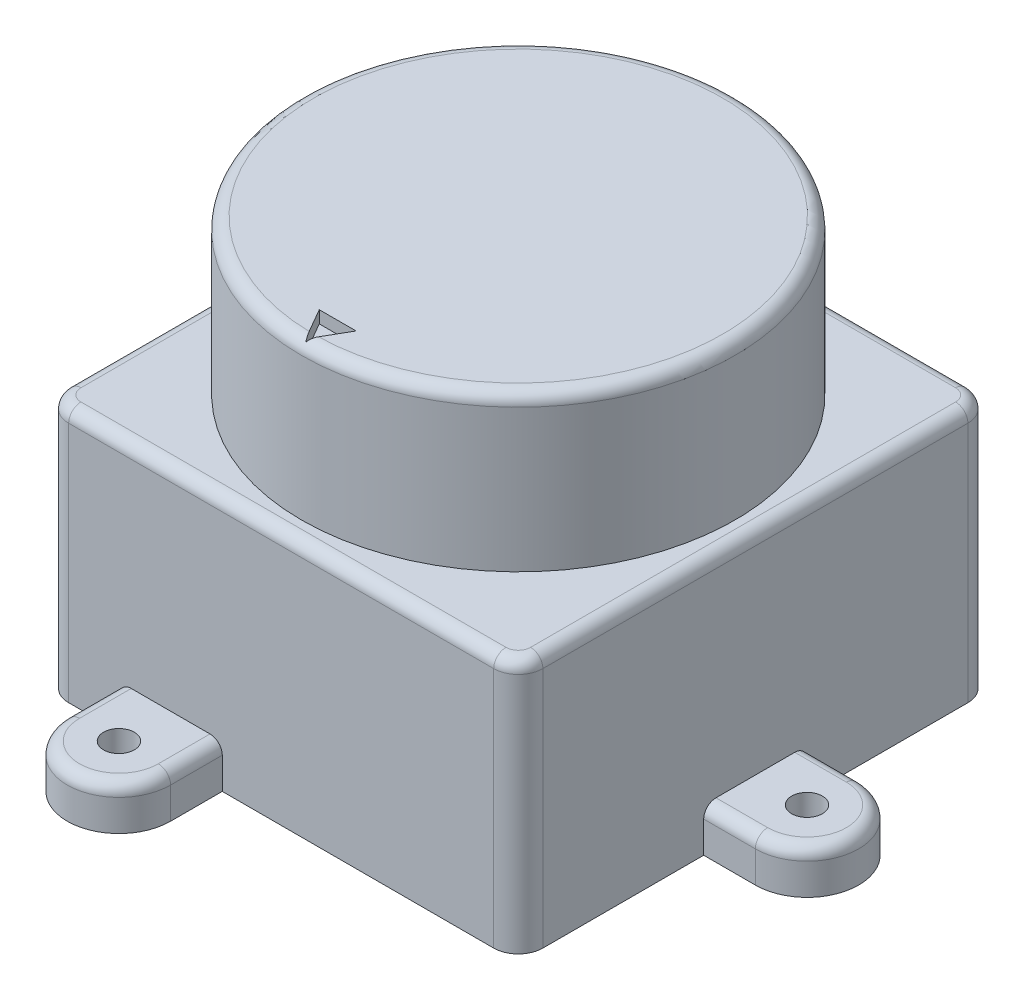
SolidWorks part; units mm, degrees
ref_plane "Front Plane" through (0, 0, 0) normal (0, 0, 1) x (1, 0, 0)
ref_plane "Top Plane" through (0, 0, 0) normal (0, 1, 0) x (1, 0, 0)
ref_plane "Right Plane" through (0, 0, 0) normal (1, 0, 0) x (0, 0, -1)
sketch "Sketch1" plane through (0, 0, 0) normal (0, 1, 0) x (1, 0, 0)
  line L1 (0, 0) -> (38.59, 0)
  line L2 (0, 0) -> (0, 38.59)
  line L3 (0, 38.59) -> (38.59, 38.59)
  line L4 (38.59, 0) -> (38.59, 38.59)
  dimension "D1" = 38.59
extrude "Boss-Extrude1" add sketch "Sketch1" along normal blind 20.7
draft "Draft1" [suppressed] type of draft neutral plane draft angle 2 faces to draft 4 reverse direction yes parameters "D1"=2
sketch "Sketch2" plane through (0, 20.7, 0) normal (0, 1, 0) x (1, 0, 0)
  line L0 (0, 38.59) -> (38.59, 0) construction
  circle A0 centre (19.295, 19.295) radius 17.645
  dimension "D1" = 35.29
extrude "Boss-Extrude2" add sketch "Sketch2" along normal blind 12.6
sketch "Sketch3" plane through (0, 33.3, 0) normal (0, 1, 0) x (1, 0, 0)
  line L0 (17.795, 4.5981) -> (19.295, 2)
  line L1 (19.295, 2) -> (20.795, 4.5981)
  line L2 (20.795, 4.5981) -> (17.795, 4.5981)
  line L3 (19.295, 38.59) -> (19.295, 2) construction
  line L4 (38.59, 38.59) -> (0, 38.59) construction
  line L5 (0, 0) -> (38.59, 0) construction
  dimension "D1" = 2
  dimension "D2" = 3
extrude "Cut-Extrude1" cut sketch "Sketch3" against normal blind 1
sketch "Sketch6" plane through (0, 0, 0) normal (1, 0, 0) x (0, 0, -1)
  line L0 (38.59, 0) -> (23.295, 1) construction
  line L1 (23.295, 5) -> (15.295, 5)
  line L2 (23.295, 5) -> (23.295, 1)
  line L3 (23.295, 1) -> (15.295, 1)
  line L4 (15.295, 5) -> (15.295, 1)
  line L5 (15.295, 1) -> (0, 0) construction
  line L6 (38.59, 0) -> (0, 0) construction
  dimension "D1" = 8
  dimension "D2" = 4
  dimension "D3" = 1
extrude "Cut-Extrude2" cut sketch "Sketch6" along normal blind 4
sketch "Sketch8" plane through (0, 0, 0) normal (0, -1, 0) x (1, 0, 0)
  line L0 (10.295, 4.205) -> (10.295, -42.795) construction
  line L1 (42.795, -19.295) -> (10.295, -19.295) construction
  line L2 (38.59, 0) -> (38.59, -38.59) construction
  line L3 (0, 0) -> (38.59, 0) construction
  line L4 (38.59, -38.59) -> (0, -38.59) construction
  line L5 (6.09, 4.205) -> (6.09, 0)
  line L6 (6.09, 0) -> (14.5, 0)
  line L7 (14.5, 0) -> (14.5, 4.205)
  line L8 (42.795, -15.09) -> (38.59, -15.09)
  line L9 (38.59, -15.09) -> (38.59, -23.5)
  line L10 (38.59, -23.5) -> (42.795, -23.5)
  line L11 (6.09, -42.795) -> (6.09, -38.59)
  line L12 (6.09, -38.59) -> (14.5, -38.59)
  line L13 (14.5, -38.59) -> (14.5, -42.795)
  circle A0 centre (10.295, 4.205) radius 4.205
  circle A1 centre (10.295, -42.795) radius 4.205
  circle A2 centre (42.795, -19.295) radius 4.205
  circle A3 centre (10.295, 4.205) radius 1.25
  circle A4 centre (42.795, -19.295) radius 1.25
  circle A5 centre (10.295, -42.795) radius 1.25
  point P8 (38.59, -19.295)
  line M10 (0, -38.59) -> (38.59, -38.59)
  line M11 (38.59, -38.59) -> (38.59, 0)
  line M12 (38.59, 0) -> (0, 0)
  dimension "D1" = 32.5
  dimension "D3" = 2.5
  dimension "D2" = 47
extrude "Boss-Extrude3" add sketch "Sketch8" against normal blind 3.55 contours A0 L5 L6 | A0 L7 M12 | A0 A3 | A2 L8 L9 | A2 L10 M11 | A2 A4 | A1 L11 M10 | A1 A5 | A1 L13 L12 region at (7.0293, 0, 0.9393) region at (13.5607, 0, -39.5293) region at (39.5293, 0, -16.0293) region at (10.295, 0, 8.2911) region at (13.5607, 0, 0.9393) region at (45.6843, 0, -16.4057) region at (39.5293, 0, -22.5607) region at (7.0293, 0, -39.5293) region at (13.1843, 0, -39.9057)
fillet "Fillet2" radius 2 4 edges at (0, 10.35, -38.59) (38.59, 10.35, -38.59) (38.59, 10.35, 0) (0, 10.35, 0)
fillet "Fillet1" radius 1 18 edges at (6.09, 3.55, -40.6925) (14.5, 3.55, -40.6925) (40.6925, 3.55, -23.5) (40.6925, 3.55, -15.09) (14.5, 3.55, 2.1025) (6.09, 3.55, 2.1025) (10.295, 3.55, -47) (47, 3.55, -19.295) (10.295, 3.55, 8.41) (38.0042, 20.7, -38.0042) (38.59, 20.7, -19.295) (38.0042, 20.7, -0.5858) (19.295, 20.7, 0) (0.5858, 20.7, -0.5858) (0, 20.7, -19.295) (0.5858, 20.7, -38.0042) (19.295, 33.3, -1.65) (19.295, 20.7, -38.59)
